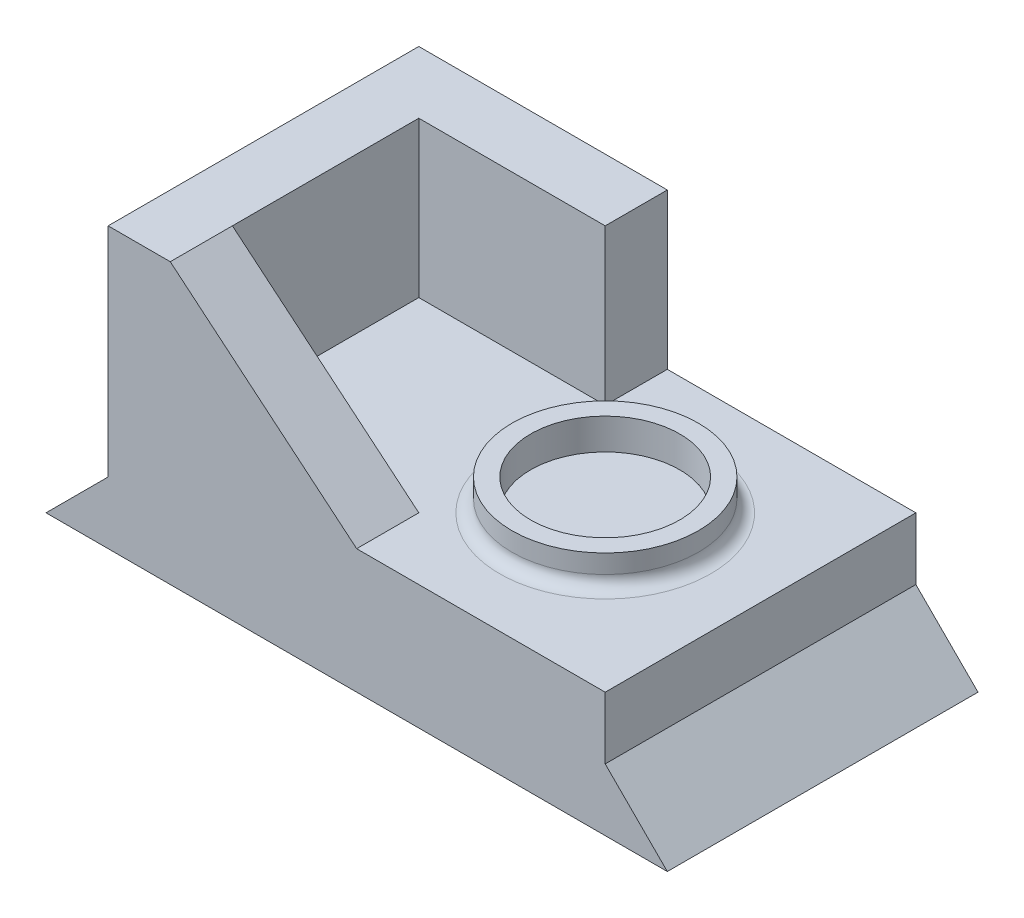
SolidWorks part; units mm, degrees
material "Alliage 1060"
ref_plane "Plan de face" through (0, 0, 0) normal (0, 0, 1) x (1, 0, 0)
ref_plane "Plan de dessus" through (0, 0, 0) normal (0, 1, 0) x (1, 0, 0)
ref_plane "Plan de droite" through (0, 0, 0) normal (1, 0, 0) x (0, 0, -1)
sketch "Esquisse1" plane through (0, 0, 0) normal (0, 0, 1) x (1, 0, 0)
  line L0 (0, 0) -> (0, 46.722) construction
  line L1 (50, 0) -> (-50, 0)
  line L2 (-50, 0) -> (-40, 10)
  line L3 (-40, 10) -> (-40, 20)
  line L4 (-40, 20) -> (40, 20)
  line L5 (40, 10) -> (40, 20)
  line L6 (50, 0) -> (40, 10)
  point P9 (0, 20)
  dimension "D1" = 50
  dimension "D2" = 10
  dimension "D3" = 10
  dimension "D4" = 10
extrude "Boss.-Extru.1" add sketch "Esquisse1" along normal blind 50
sketch "Esquisse2" plane through (0, 20, 0) normal (0, 1, 0) x (1, 0, 0)
  line L0 (-40, -50) -> (-40, 0) construction
  line L1 (-40, -50) -> (-40, 0)
  line L2 (-40, 0) -> (0, 0)
  line L3 (40, 0) -> (-40, 0) construction
  line L4 (0, 0) -> (0, -10)
  line L5 (0, -10) -> (-30, -10)
  line L6 (-30, -10) -> (-30, -40)
  line L7 (-30, -40) -> (0, -40)
  line L8 (0, -40) -> (0, -50)
  line L9 (40, -50) -> (-40, -50) construction
  line L10 (0, -50) -> (-40, -50)
  dimension "D1" = 10
  dimension "D2" = 10
  dimension "D3" = 30
extrude "Boss.-Extru.2" add sketch "Esquisse2" along normal blind 25
sketch "Esquisse3" plane through (0, 0, 50) normal (0, 0, 1) x (1, 0, 0)
  line L0 (0, 45) -> (0, 20) construction
  line L1 (-40, 45) -> (0, 45) construction
  line L2 (0, 45) -> (0, 20)
  line L3 (-30, 45) -> (0, 45)
  line L4 (-30, 45) -> (0, 20)
  dimension "D1" = 10
extrude "Enlèv. mat.-Extru.1" cut sketch "Esquisse3" against normal up to next
sketch "Esquisse4" plane through (0, 20, 0) normal (0, 1, 0) x (1, 0, 0)
  line L0 (40, -50) -> (0, -50) construction
  line L1 (40, -50) -> (40, 0) construction
  circle A0 centre (15, -25) radius 15
  circle A1 centre (15, -25) radius 12
  dimension "D2" = 25
  dimension "D3" = 30
  dimension "D4" = 24
  dimension "D1" = 25
extrude "Boss.-Extru.3" add sketch "Esquisse4" along normal blind 5
fillet "Congé1" radius 2 1 edges at (15, 20, 10)
